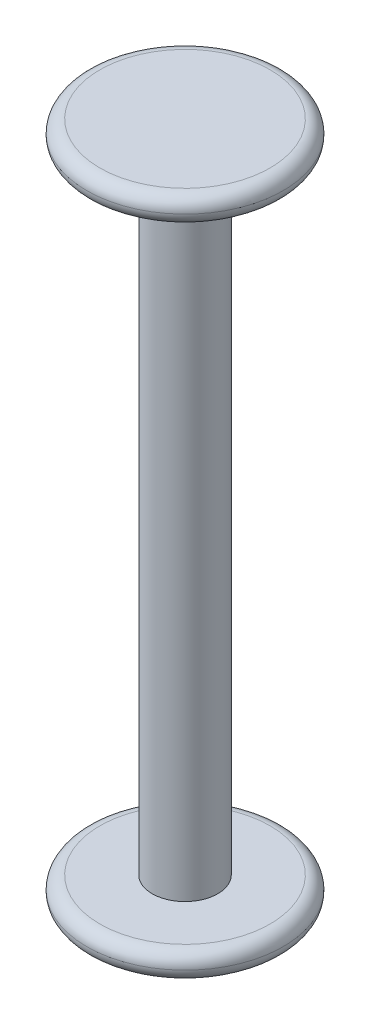
SolidWorks part; units mm, degrees
material "1060 Alloy"
ref_plane "Front Plane" through (0, 0, 0) normal (0, 0, 1) x (1, 0, 0)
ref_plane "Top Plane" through (0, 0, 0) normal (0, 1, 0) x (1, 0, 0)
ref_plane "Right Plane" through (0, 0, 0) normal (1, 0, 0) x (0, 0, -1)
sketch "Sketch1" plane through (0, 0, 0) normal (0, 1, 0) x (1, 0, 0)
  circle A0 centre (0, 0) radius 2.5
  dimension "D1" = 5
extrude "Boss-Extrude1" add sketch "Sketch1" along normal blind 24
sketch "Sketch2" plane through (0, 24, 0) normal (0, 1, 0) x (1, 0, 0)
  circle A3 centre (0, 0) radius 7.5
  point P0 (14.9477, 1.7297)
  dimension "D1" = 15
extrude "Boss-Extrude2" add sketch "Sketch2" along normal blind 2
fillet "Fillet1" radius 1 2 edges at (0, 26, 7.5) (0, 24, 7.5)
mirror "Mirror1" about plane through (0, 0, 0) normal (0, 1, 0) of bodies 102
